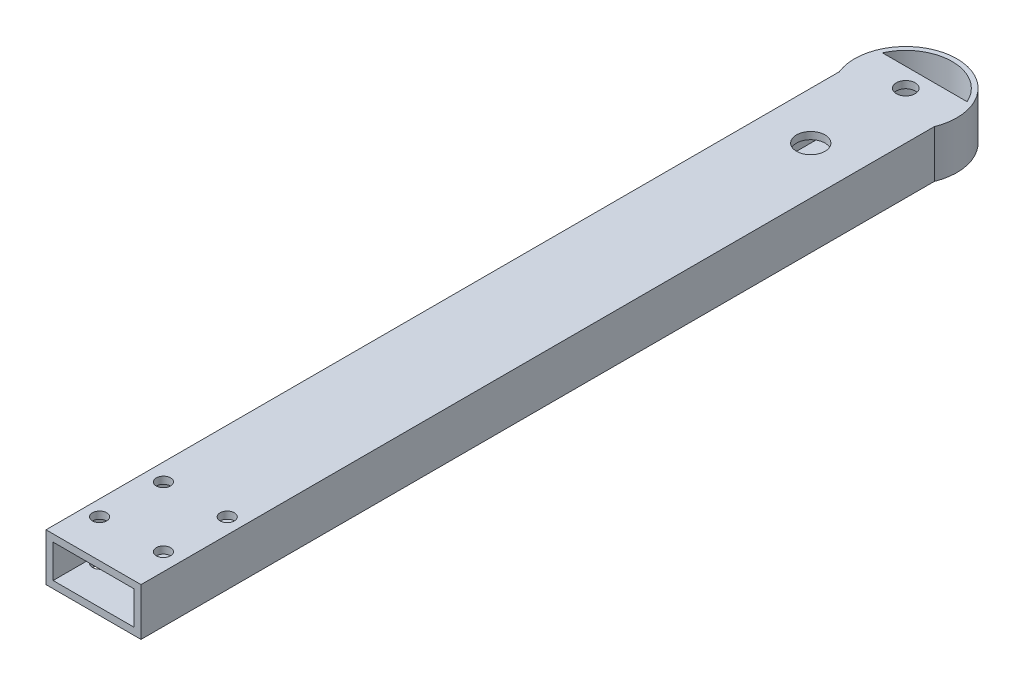
SolidWorks part; units mm, degrees
ref_plane "Front Plane" through (0, 0, 0) normal (0, 0, 1) x (1, 0, 0)
ref_plane "Top Plane" through (0, 0, 0) normal (0, 1, 0) x (1, 0, 0)
ref_plane "Right Plane" through (0, 0, 0) normal (1, 0, 0) x (0, 0, -1)
sketch "Sketch1" plane through (0, 0, 0) normal (0, 0, 1) x (1, 0, 0)
  line L0 (8.5, -3.5) -> (-8.5, -3.5)
  line L1 (10, -5) -> (-10, -5)
  line L2 (10, -5) -> (10, 5)
  line L3 (10, 5) -> (-10, 5)
  line L4 (-10, -5) -> (-10, 5)
  line L5 (10, -5) -> (-10, 5) construction
  line L6 (10, 5) -> (-10, -5) construction
  line L7 (-8.5, -3.5) -> (-8.5, 3.5)
  line L8 (8.5, 3.5) -> (-8.5, 3.5)
  line L9 (8.5, -3.5) -> (8.5, 3.5)
  point P0 (0, 0)
  dimension "D1" = 20
  dimension "D2" = 10
  dimension "D3" = 1.5
extrude "Boss-Extrude1" add sketch "Sketch1" along normal blind 175
sketch "Sketch2" plane through (0, 5, 0) normal (0, 1, 0) x (1, 0, 0)
  line L0 (0, -175) -> (0, -154.1805) construction
  line L1 (10, -175) -> (-10, -175) construction
  line L2 (6.364, -166.6464) -> (-6.364, -153.9185) construction
  line L3 (-6.7175, -167) -> (6.7175, -153.565) construction
  circle A0 centre (6.364, -166.6464) radius 1.5
  circle A1 centre (-6.7175, -167) radius 1.5
  circle A2 centre (6.7175, -153.565) radius 1.5
  circle A3 centre (-6.364, -153.9185) radius 1.5
  point P13 (0, -160.2825)
  point P14 (0, -160.2825)
  dimension "D1" = 3
  dimension "D2" = 19
  dimension "D3" = 18
  dimension "D4" = 8
extrude "Cut-Extrude1" cut sketch "Sketch2" against normal through all
sketch "Sketch3" plane through (0, 5, 0) normal (0, 1, 0) x (1, 0, 0)
  line L0 (0, -188.574) -> (0, -5.39) construction
  line L1 (-6.364, -153.9185) -> (6.364, -166.6464) construction
  line L3 (10, 0) -> (-10, 0) construction
  circle A0 centre (0, -4) radius 2
  circle A1 centre (0, -24) radius 3
  point P11 (0, -160.2825)
  dimension "D1" = 6
  dimension "D2" = 4
  dimension "D3" = 20
  dimension "D4" = 4
  dimension "D5" = 156.2825
extrude "Cut-Extrude2" cut sketch "Sketch3" against normal through all
sketch "Sketch4" plane through (0, 5, 0) normal (0, 1, 0) x (1, 0, 0)
  line L0 (0, -175) -> (0, 0) construction
  line L1 (10, -175) -> (-10, -175) construction
  circle A0 centre (0, -4) radius 2 construction
  point P5 (0, -4)
sketch "Sketch5" plane through (0, 5, 0) normal (0, 1, 0) x (1, 0, 0)
  circle A0 centre (0, -4) radius 10.7703
  circle A1 centre (0, -4) radius 9.7703
  dimension "D1" = 1
extrude "Boss-Extrude2" add sketch "Sketch5" against normal blind 10
ref_axis "Axis1" through (0, 3.5, 4) along (0, 1, 0)
